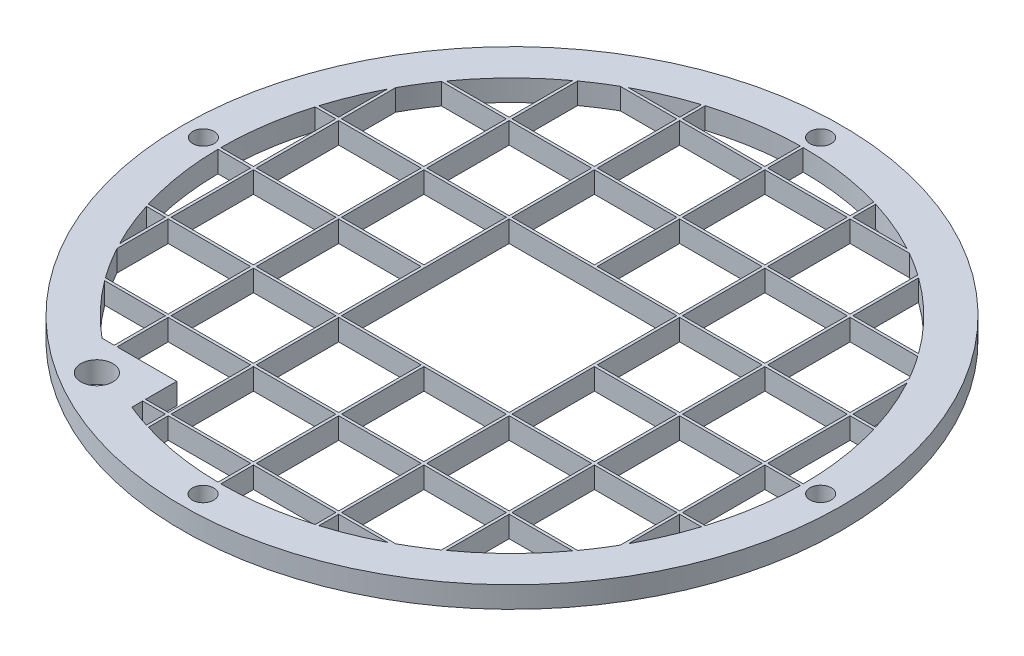
SolidWorks part; units mm, degrees
ref_plane "Front Plane" through (0, 0, 0) normal (0, 0, 1) x (1, 0, 0)
ref_plane "Top Plane" through (0, 0, 0) normal (0, 1, 0) x (1, 0, 0)
ref_plane "Right Plane" through (0, 0, 0) normal (1, 0, 0) x (0, 0, -1)
sketch "Sketch2" plane through (0, 0, 0) normal (0, 1, 0) x (1, 0, 0)
  circle A1 centre (0, 0) radius 41
  circle A2 centre (0, 0) radius 46
  point P208 (0, 0)
extrude "Boss-Extrude2" add sketch "Sketch2" along normal blind 3
sketch "Sketch4" plane through (0, 3, 0) normal (0, 1, 0) x (1, 0, 0)
  line L0 (0, 46) -> (0, 12)
  line L1 (12, 44.4072) -> (12, -44.4072)
  line L2 (24, 39.2428) -> (24, -39.2428)
  line L3 (36, 28.6356) -> (36, -28.6356)
  line L4 (-12, 44.4072) -> (-12, -44.4072)
  line L5 (-24, 39.2428) -> (-24, -32)
  line L6 (-36, 28.6356) -> (-36, -28.6356)
  line L7 (-46, 0) -> (-12, 0)
  line L8 (-44.4072, -12) -> (44.4072, -12)
  line L9 (-39.2428, -24) -> (39.2428, -24)
  line L10 (12, 0) -> (46, 0)
  line L11 (-44.4072, 12) -> (44.4072, 12)
  line L12 (-39.2428, 24) -> (39.2428, 24)
  line L13 (-28.6356, 36) -> (28.6356, 36)
  line L14 (-16, -36) -> (28.6356, -36)
  line L15 (0, -12) -> (0, -46)
  line L50 (-26.0661, -32) -> (-16, -32)
  line L52 (-26.0661, -32) -> (-26.0661, -37.902)
  line L60 (-16, -32) -> (-16, -43.1277)
  line L61 (-28.6356, -36) -> (-26.0661, -36) [skipped]
  circle A1 centre (0, 0) radius 46 construction
  circle A2 centre (0, 0) radius 46
  dimension "D1" = 4
  dimension "D2" = 4
extrude "Extrude-Thin5" add sketch "Sketch4" against normal blind 3 thin thin type one direction wall 0.4
sketch "Sketch5" plane through (0, 0, 0) normal (0, -1, 0) x (1, 0, 0)
  circle A0 centre (0, -43.4524) radius 1.5
  circle A1 centre (-43.4524, 0) radius 1.5
  circle A3 centre (43.4524, 0) radius 1.5
  circle A4 centre (0, 43.4524) radius 1.5 [skipped]
  point P11 (0, 0)
  dimension "D1" = 4
extrude "Cut-Extrude1" cut sketch "Sketch5" against normal blind 3
sketch "Sketch6" plane through (0, 3, 0) normal (0, 1, 0) x (1, 0, 0)
  circle A1 centre (0, -43.5) radius 1.5
  point P36 (0, 3)
  dimension "D1" = 43.5
extrude "Cut-Extrude2" cut sketch "Sketch6" against normal through all
sketch "Sketch8" plane through (0, 3, 0) normal (0, 1, 0) x (1, 0, 0)
  line L1 (-16, -32) -> (-25.632, -32)
  line L2 (-16, -32) -> (-16, -37.7492)
  line L3 (-16, -37.7492) -> (-25.632, -37.7492)
  line L4 (-25.632, -32) -> (-25.632, -37.7492)
  point P4 (-16, -32)
  point P5 (-25.632, -32)
  point P6 (-16, -37.7492)
extrude "Boss-Extrude4" add sketch "Sketch8" against normal through all
sketch "Sketch9" plane through (0, 3, 0) normal (0, 1, 0) x (1, 0, 0)
  circle A3 centre (-22.2697, -36.1812) radius 2.25
extrude "Cut-Extrude3" cut sketch "Sketch9" against normal through all
